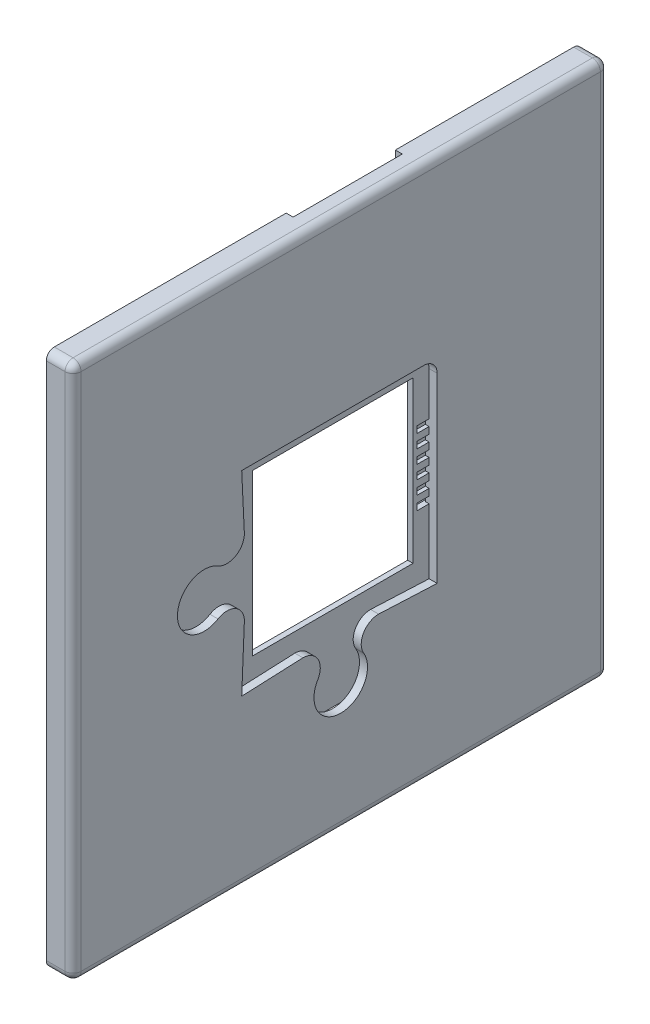
SolidWorks part; units mm, degrees
ref_plane "Front Plane" through (0, 0, 0) normal (0, 0, 1) x (1, 0, 0)
ref_plane "Top Plane" through (0, 0, 0) normal (0, 1, 0) x (1, 0, 0)
ref_plane "Right Plane" through (0, 0, 0) normal (1, 0, 0) x (0, 0, -1)
sketch "Sketch1" plane through (0, 0, 0) normal (1, 0, 0) x (0, 0, -1)
  line L1 (-100, 100) -> (100, 100)
  line L2 (-100, 100) -> (-100, -100)
  line L3 (-100, -100) -> (100, -100)
  line L4 (100, 100) -> (100, -100)
  point P6 (-100, 0)
  dimension "D1" = 200
  dimension "D2" = 200
  dimension "D3" = 100
extrude "Boss-Extrude1" add sketch "Sketch1" along normal blind 10
sketch "Sketch2" plane through (0, 0, 0) normal (-1, 0, 0) x (0, 0, 1)
  line L0 (-35.5, 35.5) -> (-25.5, 35.5)
  line L1 (-35.5, 35.5) -> (-25.5, 35.5)
  line L2 (-35.5, 35.5) -> (-35.5, -35.5)
  line L3 (-35.5, -35.5) -> (35.5, -35.5)
  line L4 (35.5, 35.5) -> (35.5, -35.5)
  line L5 (-25.5, 35.5) -> (-5, 44.5)
  line L6 (-5, 44.5) -> (5, 44.5)
  line L7 (5, 44.5) -> (25.5, 35.5)
  line L8 (25.5, 35.5) -> (35.5, 35.5)
  line L9 (25.5, 35.5) -> (35.5, 35.5)
  line L10 (36.5, 35.5) -> (36.5, -36.5)
  line L11 (-36.5, -36.5) -> (36.5, -36.5)
  line L12 (-36.5, 35.5) -> (-36.5, -36.5)
  line L13 (-35.5, 36.5) -> (-25.5, 36.5)
  line L14 (-25.902, 36.4156) -> (-5.2098, 45.5)
  line L15 (-5.2098, 45.5) -> (5.2098, 45.5)
  line L16 (5.2098, 45.5) -> (25.902, 36.4156)
  line L17 (25.5, 36.5) -> (35.5, 36.5)
  line L18 (-36.5, 35.5) -> (-36.5, 36.5)
  line L19 (-36.5, 36.5) -> (-35.5, 36.5)
  line L20 (35.5, 36.5) -> (36.5, 36.5)
  line L21 (36.5, 36.5) -> (36.5, 35.5)
  point P5 (0, -35.5)
  point P12 (35.5, 0)
  dimension "D1" = 10
  dimension "D2" = 71
  dimension "D3" = 71
  dimension "D4" = 10
  dimension "D5" = 10
  dimension "D6" = 80
  dimension "D7" = 20.5
  dimension "D8" = 1
extrude "Cut-Extrude1" cut sketch "Sketch2" against normal blind 5 contours L21 L20 L17 L16 L15 L14 L13 L19 L18 L12 L11 L10 L7 L8 L4 L3 L2 L0 L5 L6 | L8 L7 L6 L5 L0 L2 L3 L4 region at (0, 2.0136, 0) region at (0, -0.5, 36.3902)
sketch "Sketch3" plane through (5, 0, 0) normal (-1, 0, 0) x (0, 0, 1)
  line L1 (-30, 30) -> (30, 30)
  line L2 (-30, 30) -> (-30, -30)
  line L3 (-30, -30) -> (30, -30)
  line L4 (30, 30) -> (30, -30)
  point P4 (0, -30)
  point P6 (30, 0)
  dimension "D1" = 60
  dimension "D2" = 60
extrude "Cut-Extrude2" cut sketch "Sketch3" against normal through all
sketch "Sketch4" plane through (10, 0, 0) normal (1, 0, 0) x (0, 0, -1)
  line L2 (-36, 35) -> (-36, 14.1421) construction
  line L3 (-36, -37) -> (-14.1421, -37) construction
  line L8 (36, 30) -> (36, -37)
  line L9 (37, -38) -> (-37, -38) construction
  line L10 (-37, 37) -> (37, 37) construction
  line L11 (-37, 37) -> (-37, -38) construction
  line L13 (37, 37) -> (37, -38) construction
  line L14 (14.1421, -37) -> (36, -37) construction
  line L15 (31, 35) -> (-36, 35)
  line L16 (-36, -14.1421) -> (-36, -37) construction
  line L17 (-36, 14.1421) -> (-37, 35)
  line L18 (-37, 35) -> (-36, 35)
  line L19 (-14.1421, -37) -> (-37, -38)
  line L20 (-37, -38) -> (-36, -14.1421)
  line L21 (14.1421, -37) -> (36, -38)
  line L22 (36, -38) -> (36, -37)
  arc A6 (-8.571, -46.8485) -> (8.571, -46.8485) centre (0, -52) ccw
  arc A7 (14.1421, -37) -> (8.571, -46.8485) centre (14.1421, -43.5) ccw
  arc A8 (-8.571, -46.8485) -> (-14.1421, -37) centre (-14.1421, -43.5) ccw
  arc A9 (-45.8485, 8.571) -> (-36, 14.1421) centre (-42.5, 14.1421) ccw
  arc A10 (-36, -14.1421) -> (-45.8485, -8.571) centre (-42.5, -14.1421) ccw
  arc A11 (-45.8485, 8.571) -> (-45.8485, -8.571) centre (-51, 0) ccw
  arc A12 (31, 35) -> (36, 30) centre (31, 30) cw
  point P9 (36, 35)
  point P22 (0.5, -0.5)
  point P24 (0, 0)
  dimension "D3" = 2
  dimension "D4" = 2
  dimension "D6" = 15
  dimension "D8" = 1
  dimension "D9" = 1
  dimension "D12" = 20
  dimension "D13" = 13
  dimension "D14" = 13
  dimension "D7" = 20.8579
  dimension "D5" = 5
  dimension "D1" = 72
  dimension "D2" = 72
  dimension "D10" = 1
  dimension "D11" = 15
  dimension "D15" = 36
extrude "Cut-Extrude3" cut sketch "Sketch4" against normal blind 3
sketch "Sketch8" plane through (0, 0, 0) normal (-1, 0, 0) x (0, 0, 1)
  line L0 (20, 86) -> (-20, 86) construction
  line L1 (10.4, 100) -> (-30.4, 100)
  line L2 (10.4, 100) -> (10.4, 86.4)
  line L3 (10.4, 86.4) -> (-30.4, 86.4)
  line L4 (-30.4, 100) -> (-30.4, 86.4)
  line L5 (-100, -100) -> (-100, 100) construction
  line L6 (-100, 100) -> (100, 100) construction
  dimension "D1" = 0.4
  dimension "D2" = 69.6
  dimension "D3" = 40.8
extrude "Cut-Extrude4" cut sketch "Sketch8" against normal blind 2.6
shell "Shell1" [suppressed] thickness 5
sketch "Sketch9" plane through (0, 0, 0) normal (-1, 0, 0) x (0, 0, 1)
  line L0 (-95, 95) -> (-95, -95)
  line L1 (-95, -95) -> (95, -95)
  line L2 (95, -95) -> (95, 95)
  line L3 (95, 95) -> (15.4, 95)
  line L4 (15.4, 95) -> (15.4, 81.4)
  line L5 (15.4, 81.4) -> (-35.4, 81.4)
  line L6 (-35.4, 81.4) -> (-35.4, 95)
  line L7 (-35.4, 95) -> (-95, 95)
  line L8 (-41.5, 41.5) -> (-41.5, -41.5)
  line L9 (-41.5, -41.5) -> (41.5, -41.5)
  line L10 (41.5, -41.5) -> (41.5, 41.5)
  line L14 (-100, -100) -> (-100, 100) construction
  line L15 (-100, 100) -> (-30.4, 100) construction
  line L16 (-30.4, 100) -> (-30.4, 86.4) construction
  line L17 (10.4, 86.4) -> (10.4, 100) construction
  line L18 (-30.4, 86.4) -> (10.4, 86.4) construction
  line L19 (100, 100) -> (100, -100) construction
  line L20 (100, -100) -> (-100, -100) construction
  line L21 (-36.5, -36.5) -> (-36.5, 36.5) construction
  line L22 (-36.5, -36.5) -> (36.5, -36.5) construction
  line L23 (36.5, 36.5) -> (36.5, -36.5) construction
  line L24 (-5.2098, 45.5) -> (5.2098, 45.5)
  line L27 (-41.5, 41.5) -> (-19.2962, 41.5)
  line L28 (-19.2962, 41.5) -> (-5.6295, 47.5)
  line L29 (-5.6295, 47.5) -> (5.6295, 47.5) construction
  line L30 (5.6295, 47.5) -> (19.2962, 41.5)
  line L32 (19.2962, 41.5) -> (41.5, 41.5)
  line L33 (-36.5, 36.5) -> (-25.7098, 36.5) construction
  line L35 (-25.7098, 36.5) -> (-5.2098, 45.5) construction
  line L36 (5.2098, 45.5) -> (25.7098, 36.5) construction
  line L37 (-5.2098, 45.5) -> (5.2098, 45.5) construction
  line L38 (5.2098, 45.5) -> (25.7098, 36.5) construction
  line L39 (25.7098, 36.5) -> (36.5, 36.5) construction
  line L40 (-25.7098, 36.5) -> (-5.2098, 45.5) construction
  line L41 (-12.5, -41.5) -> (-12.5, -61.5)
  line L42 (-12.5, -61.5) -> (12.5, -61.5)
  line L43 (12.5, -61.5) -> (12.5, -41.5)
  line L44 (41.5, 12.5) -> (61.5, 12.5)
  line L45 (61.5, 12.5) -> (61.5, -12.5)
  line L46 (61.5, -12.5) -> (41.5, -12.5)
  line L47 (-5.2098, 45.5) -> (-5.6295, 47.5)
  line L48 (5.2098, 45.5) -> (5.6295, 47.5)
  point P59 (61.5, 0)
  point P62 (41.5, 0)
  point P63 (0, -61.5)
  point P64 (0, -41.5)
  line M34 (-5.2098, 45.5) -> (5.2098, 45.5)
  dimension "D1" = 5
  dimension "D2" = 5
  dimension "D3" = 5
  dimension "D4" = 5
  dimension "D5" = 5
  dimension "D6" = 5
  dimension "D7" = 5
  dimension "D8" = 5
  dimension "D9" = 5
  dimension "D10" = 5
  dimension "D11" = 5
  dimension "D12" = 5
  dimension "D13" = 2
  dimension "D14" = 2
  dimension "D15" = 5
  dimension "D16" = 2
  dimension "D17" = 25
  dimension "D18" = 25
  dimension "D19" = 20
  dimension "D20" = 20
extrude "Cut-Extrude5" cut sketch "Sketch9" against normal blind 7 contours L6 L7 L0 L1 L2 L3 L4 L5 L45 L46 L10 L9 L43 L42 L41 L8 L27 L28 L29 L30 L32 L44 | L29 L47 L48 M34 region at (0, 92.313, -65.2) region at (0, 46.5129, 0)
fillet "Fillet1" radius 3 8 edges at (5, 100, 100) (5, -100, 100) (10, 0, -100) (10, 100, 0) (10, 0, 100) (10, -100, 0) (5, 100, -100) (5, -100, -100)
sketch "Sketch10" plane through (0, -61.5, 0) normal (0, -1, 0) x (1, 0, 0)
  line L0 (7, -12.5) -> (7, -3.1225) construction
  line L1 (2.7, -2.6) -> (5.8, -2.6)
  line L2 (2.7, -2.6) -> (2.7, 2.6)
  line L3 (2.7, 2.6) -> (5.8, 2.6)
  line L4 (5.8, -2.6) -> (5.8, 2.6)
  line L6 (7, -12.5) -> (0, -12.5) construction
  point P8 (2.7, 0)
  dimension "D1" = 5.2
  dimension "D2" = 3.1
  dimension "D3" = 1.2
  dimension "D4" = 12.5
extrude "Cut-Extrude6" cut sketch "Sketch10" against normal blind 15
fillet "Fillet2" radius 1 4 edges at (4.25, -61.5, -2.6) (5.8, -61.5, 0) (4.25, -61.5, 2.6) (2.7, -61.5, 0)
sketch "Sketch11" plane through (0, 0, 61.5) normal (0, 0, 1) x (1, 0, 0)
  line L1 (2.7, 2.6) -> (5.8, 2.6)
  line L2 (2.7, 2.6) -> (2.7, -2.6)
  line L3 (2.7, -2.6) -> (5.8, -2.6)
  line L4 (5.8, 2.6) -> (5.8, -2.6)
  line L5 (7, -12.5) -> (0, -12.5) construction
  line L6 (7, 12.5) -> (7, -12.5) construction
  point P4 (2.7, 0)
  dimension "D1" = 3.1
  dimension "D2" = 5.2
  dimension "D3" = 12.5
  dimension "D4" = 1.2
extrude "Cut-Extrude7" cut sketch "Sketch11" against normal blind 15
fillet "Fillet3" radius 1 4 edges at (2.7, 0, 61.5) (4.25, -2.6, 61.5) (5.8, 0, 61.5) (4.25, 2.6, 61.5)
fillet "Fillet4" radius 4 4 edges at (3.5, 12.5, 61.5) (3.5, -12.5, 61.5) (3.5, -61.5, 12.5) (3.5, -61.5, -12.5)
sketch "Sketch12" plane through (0, 0, 0) normal (-1, 0, 0) x (0, 0, 1)
  line L0 (-95, 95) -> (-95, -95) construction
  line L1 (-95, -84.8) -> (-99, -84.8)
  line L2 (-95, -84.8) -> (-95, -90)
  line L3 (-95, -90) -> (-99, -90)
  line L4 (-99, -84.8) -> (-99, -90)
  line L5 (-100, -97) -> (-100, 97) construction
  line L6 (97, -100) -> (-97, -100) construction
  dimension "D1" = 1
  dimension "D2" = 10
  dimension "D3" = 5.2
extrude "Cut-Extrude8" cut sketch "Sketch12" against normal blind 2
sketch "Sketch13" plane through (2, 0, 0) normal (-1, 0, 0) x (0, 0, 1)
  line L0 (-99, -90) -> (-95, -90) construction
  line L1 (-99, -84.8) -> (-96, -84.8)
  line L2 (-99, -84.8) -> (-99, -90)
  line L3 (-99, -90) -> (-96, -90)
  line L4 (-96, -84.8) -> (-96, -90)
  dimension "D1" = 3
extrude "Cut-Extrude9" cut sketch "Sketch13" against normal blind 6
sketch "Sketch14" plane through (7, 0, 0) normal (-1, 0, 0) x (0, 0, 1)
  line L0 (95, -95) -> (95, 95) construction
  line L1 (95, -82.4) -> (92, -82.4)
  line L2 (95, -82.4) -> (95, -92.4)
  line L3 (95, -92.4) -> (92, -92.4)
  line L4 (92, -82.4) -> (92, -92.4)
  line L5 (-99, -84.8) -> (-99, -90) construction
  point P8 (-99, -87.4)
  point P9 (92, -87.4)
  dimension "D1" = 10
  dimension "D2" = 3
extrude "Boss-Extrude2" add sketch "Sketch14" along normal blind 7
sketch "Sketch16" plane through (0, 0, 92) normal (0, 0, -1) x (-1, 0, 0)
  line L0 (0, -82.4) -> (0, -92.4) construction
  line L1 (-4.4, -84.9) -> (-1.2, -84.9)
  line L2 (-4.4, -84.9) -> (-4.4, -89.9)
  line L3 (-4.4, -89.9) -> (-1.2, -89.9)
  line L4 (-1.2, -84.9) -> (-1.2, -89.9)
  point P6 (0, -87.4)
  point P7 (-1.2, -87.4)
  dimension "D1" = 3.2
  dimension "D2" = 1.2
  dimension "D3" = 5
extrude "Cut-Extrude10" cut sketch "Sketch16" against normal blind 6
fillet "Fillet5" radius 1 3 edges at (2.8, -89.9, 92) (4.4, -87.4, 92) (2.8, -84.9, 92)
sketch "Sketch17" plane through (0, 0, 0) normal (-1, 0, 0) x (0, 0, 1)
  line L1 (-65.5796, 65.977) -> (65.5796, 65.977)
  line L2 (-65.5796, 65.977) -> (-65.5796, -65.977)
  line L3 (-65.5796, -65.977) -> (65.5796, -65.977)
  line L4 (65.5796, 65.977) -> (65.5796, -65.977)
  point P4 (0, 65.977)
  point P6 (-65.5796, 0)
  dimension "D1" = 131.954
  dimension "D2" = 131.1591
extrude "Cut-Extrude11" cut sketch "Sketch17" against normal blind 2.1
sketch "Sketch18" plane through (0, 0, 0) normal (-1, 0, 0) x (0, 0, 1)
  line L0 (97, -82.4) -> (97, 97)
  line L1 (97, 97) -> (13.4, 97)
  line L2 (13.4, 97) -> (13.4, 83.4)
  line L3 (13.4, 83.4) -> (-33.4, 83.4)
  line L4 (-33.4, 83.4) -> (-33.4, 97)
  line L5 (-33.4, 97) -> (-97, 97)
  line L6 (-97, 97) -> (-97, -84.8)
  line L7 (-97, -90) -> (-97, -97)
  line L28 (-97, -97) -> (97, -97)
  line L30 (15.4, 95) -> (15.4, 81.4) construction
  line L31 (15.4, 81.4) -> (-35.4, 81.4) construction
  line L32 (97, -97) -> (97, -92.4)
  line L33 (-35.4, 95) -> (-95, 95) construction
  line L34 (-95, 95) -> (-95, -84.8) construction
  line L35 (97, -82.4) -> (97, -92.4)
  line L36 (95, -82.4) -> (95, 95) construction
  line L37 (95, -95) -> (95, -92.4) construction
  line L39 (-35.4, 81.4) -> (-35.4, 95) construction
  line L43 (-95, -90) -> (-95, -95) construction
  line L44 (-95, -95) -> (95, -95) construction
  line L47 (95, 95) -> (15.4, 95) construction
  line L48 (15.4, 81.4) -> (-35.4, 81.4)
  line L49 (-35.4, 81.4) -> (-35.4, 95)
  line L50 (-35.4, 95) -> (-95, 95)
  line L51 (-95, 95) -> (-95, -84.8)
  line L55 (-95, -90) -> (-95, -95)
  line L56 (-95, -95) -> (95, -95)
  line L57 (95, -95) -> (95, -92.4)
  line L61 (95, -82.4) -> (95, 95)
  line L62 (15.4, 95) -> (15.4, 81.4)
  line L63 (95, 95) -> (15.4, 95)
  line L64 (-97, -90) -> (-97, -84.8)
  line L65 (-95, -84.8) -> (-95, -90)
  line L66 (95, -82.4) -> (95, -92.4)
  line M19 (-95, -95) -> (-95, -90)
  line M20 (-95, -90) -> (-99, -90)
  line M22 (-99, -84.8) -> (-95, -84.8)
  line M23 (-95, -84.8) -> (-95, 95)
  line M24 (-95, 95) -> (-35.4, 95)
  line M25 (-35.4, 95) -> (-35.4, 81.4)
  line M26 (-35.4, 81.4) -> (15.4, 81.4)
  line M27 (15.4, 81.4) -> (15.4, 95)
  line M28 (15.4, 95) -> (95, 95)
  line M29 (95, 95) -> (95, -82.4)
  line M30 (95, -82.4) -> (92, -82.4)
  line M31 (92, -82.4) -> (92, -92.4)
  line M32 (92, -92.4) -> (95, -92.4)
  line M33 (95, -92.4) -> (95, -95)
  line M34 (95, -95) -> (-95, -95)
  dimension "D1" = 2
extrude "Cut-Extrude12" cut sketch "Sketch18" against normal blind 2 contours L66 L7 L28 L32 L35 L0 L1 L2 L3 L4 L5 L6 M29 M33 M34 M19 M20 M22 M23 M24 M25 M26 M27 M28 | L66 M30 M31 M32 region at (0, -87.4, 96.7256) region at (0, -87.4, 93.5)
sketch "Sketch19" plane through (7, 0, 0) normal (1, 0, 0) x (0, 0, -1)
  line L0 (36, -38) -> (36, 30) construction
  line L1 (36, 13.75) -> (31.5, 13.75)
  line L2 (36, 13.75) -> (36, -13.75)
  line L3 (36, -13.75) -> (31.5, -13.75)
  line L4 (31.5, 13.75) -> (31.5, -13.75)
  line L6 (36, 13.75) -> (31.5, 13.75)
  line L7 (36, 13.75) -> (36, 11.25)
  line L8 (36, 11.25) -> (31.5, 11.25)
  line L9 (31.5, 13.75) -> (31.5, 11.25)
  line L10 (36, 8.75) -> (31.5, 8.75)
  line L11 (36, 8.75) -> (36, 6.25)
  line L12 (36, 6.25) -> (31.5, 6.25)
  line L13 (31.5, 8.75) -> (31.5, 6.25)
  line L14 (36, 3.75) -> (31.5, 3.75)
  line L15 (36, 3.75) -> (36, 1.25)
  line L16 (36, 1.25) -> (31.5, 1.25)
  line L17 (31.5, 3.75) -> (31.5, 1.25)
  line L18 (36, -1.25) -> (31.5, -1.25)
  line L19 (36, -1.25) -> (36, -3.75)
  line L20 (36, -3.75) -> (31.5, -3.75)
  line L21 (31.5, -1.25) -> (31.5, -3.75)
  line L22 (36, -6.25) -> (31.5, -6.25)
  line L23 (36, -6.25) -> (36, -8.75)
  line L24 (36, -8.75) -> (31.5, -8.75)
  line L25 (31.5, -6.25) -> (31.5, -8.75)
  line L26 (36, -11.25) -> (31.5, -11.25)
  line L27 (36, -11.25) -> (36, -13.75)
  line L28 (36, -13.75) -> (31.5, -13.75)
  line L29 (31.5, -11.25) -> (31.5, -13.75)
  line L30 (30, -30) -> (30, 30) construction
  point P25 (31.5, 0)
  line M32 (36, -38) -> (36, 30)
  dimension "D2" = 2.5
  dimension "D3" = 2.5
  dimension "D4" = 2.5
  dimension "D5" = 2.5
  dimension "D6" = 2.5
  dimension "D7" = 2.5
  dimension "D8" = 2.5
  dimension "D9" = 2.5
  dimension "D10" = 2.5
  dimension "D11" = 2.5
  dimension "D12" = 2.5
  dimension "D13" = 1.5
extrude "Cut-Extrude13" cut sketch "Sketch19" against normal through all contours L26 L4 L3 M32 | L24 L2 L22 L4 | L20 L2 L18 L4 | L16 L2 L14 L4 | L12 L2 L10 L4 | L8 L2 L1 L4 region at (7, 12.5, -33.75) region at (7, 7.5, -33.75) region at (7, 2.5, -33.75) region at (7, -2.5, -33.75) region at (7, -7.5, -33.75) region at (7, -12.5, -33.75)
sketch "Sketch20" plane through (2.1, 0, 0) normal (-1, 0, 0) x (0, 0, 1)
  line L0 (-41.5, 41.5) -> (-41.5, -41.5) construction
  line L1 (-31.5, 13.75) -> (-41.5, 13.75)
  line L2 (-31.5, 13.75) -> (-31.5, -13.75)
  line L3 (-31.5, -13.75) -> (-41.5, -13.75)
  line L4 (-41.5, 13.75) -> (-41.5, -13.75)
  line L5 (-31.5, -13.75) -> (-36, -13.75) construction
  line L6 (-31.5, -13.75) -> (-31.5, -11.25) construction
extrude "Cut-Extrude14" cut sketch "Sketch20" against normal blind 3.5
chamfer "Chamfer1" distance 0.6 angle 45 1 edges at (5, 0, -31.5)
sketch "Sketch21" plane through (0, 0, -41.5) normal (0, 0, -1) x (-1, 0, 0)
  line L0 (-5.6, 13.75) -> (-5.6, -13.75) construction
  line L2 (-1.6, 17.75) -> (-1.6, -17.75)
  line L3 (-1.6, -17.75) -> (-5.6, -17.75)
  line L4 (-5.6, 17.75) -> (-5.6, -17.75)
  line L6 (-5.6, -13.75) -> (-2.1, -13.75) construction
  line L7 (0, 22.75) -> (-2.1, 22.75)
  line L8 (0, -97) -> (0, 97) construction
  line L10 (-2.1, 17.75) -> (-1.6, 17.75)
  line L11 (-2.1, 13.75) -> (-2.1, 41.5) construction
  line L12 (-2.1, 17.75) -> (-5.6, 17.75)
  line L13 (0, 22.75) -> (0, -22.75)
  line L14 (-2.1, 22.75) -> (-2.1, 17.75)
  line L16 (-2.1, -17.75) -> (-1.6, -17.75)
  line L17 (-1.6, -17.75) -> (-1.6, 17.75)
  line L18 (-2.1, -17.75) -> (-2.1, -22.75)
  line L19 (-2.1, -41.5) -> (-2.1, -13.75) construction
  line L20 (-2.1, -22.75) -> (0, -22.75)
  line L21 (-5.6, 17.75) -> (-1.6, 17.75)
  line L22 (-1.6, 13.75) -> (-2.1, 13.75)
  line L23 (-2.1, -13.75) -> (-1.6, -13.75)
  line L24 (-2.1, 13.75) -> (-2.1, 17.75)
  line L25 (-2.1, -36.5) -> (-2.1, 36.5) construction
  line L26 (-5.6, 13.75) -> (-2.1, 13.75) construction
  point P14 (-2.1247, -17.75)
  point P15 (-2.1, -22.75)
  point P19 (-2.1, 13.6807)
  point P22 (-2.1, -17.75)
  point P26 (-3.6, -17.75)
  point P27 (-1.6, 13.6807)
  point P28 (-2.1, 13.6807)
  point P30 (-2.1, 13.7638)
  point P38 (-1.6, 13.6797)
  point P39 (-2.1, 13.5733)
  point P40 (-1.6, 13.7414)
  point P41 (-2.1, 13.7414)
  point P42 (-2.1, 13.7414)
  point P43 (0, 0)
  line M5 (-2.1, -13.75) -> (-5.6, -13.75)
  line M6 (-5.6, -13.75) -> (-5.6, 13.75)
  line M7 (-5.6, 13.75) -> (-2.1, 13.75)
  line M8 (-2.1, 13.75) -> (-2.1, 41.5)
  line M12 (-2.1, -41.5) -> (-2.1, -13.75)
  dimension "D1" = 4
  dimension "D2" = 0.5
  dimension "D3" = 4
  dimension "D4" = 5
  dimension "D5" = 4
  dimension "D6" = 5
  dimension "D7" = 4
  dimension "D8" = 5
extrude "Cut-Extrude15" cut sketch "Sketch21" against normal blind 3 contours L3 L2 M8 M7 M6 M5 M12 | L4 L3 M5 M12 | L4 M7 M8 region at (3.6, 0, -41.5) region at (3.85, 15.75, -41.5) region at (3.85, -15.75, -41.5)
extrude "Boss-Extrude4" add sketch "Sketch21<3>" against normal blind 5 contours L20 L13 L7 L2 L3 M12 M8 | L23 L3 L2 M12 | L2 M8 region at (0.8675, 0, -41.5) region at (1.85, 15.75, -41.5) region at (1.85, -15.75, -41.5)
sketch "Sketch21<3>" plane through (0, 0, -41.5) normal (0, 0, -1) x (-1, 0, 0) same geometry as "Sketch21"
chamfer "Chamfer2" distance 0.5 angle 45 8 edges at (1.85, -13.75, -41.5) (2.1, -15.75, -41.5) (3.85, -17.75, -41.5) (1.6, 0, -41.5) (2.1, 15.75, -41.5) (5.6, 0, -41.5) (1.85, 13.75, -41.5) (3.85, 17.75, -41.5)
sketch "Sketch24" plane through (7, 0, 0) normal (-1, 0, 0) x (0, 0, 1)
  line L0 (-95, 95) -> (95, -95) construction
  line L1 (-95, -95) -> (95, 95) construction
  circle A0 centre (80, -80) radius 5
  circle A1 centre (80, -80) radius 1.25
  circle A2 centre (-80, -80) radius 1.25
  circle A3 centre (-80, -80) radius 5
  dimension "D1" = 10
  dimension "D2" = 2.5
  dimension "D4" = 2.5
  dimension "D5" = 10
  dimension "D3" = 15
  dimension "D6" = 15
extrude "Boss-Extrude5" add sketch "Sketch24" along normal blind 5
mirror "Mirror1" about plane through (0, 0, 0) normal (0, 1, 0) of "Boss-Extrude5"
sketch "Sketch25" plane through (2.1, 0, 0) normal (-1, 0, 0) x (0, 0, 1)
  line L0 (36.5, 36.5) -> (41.5, 41.5) construction
  line L1 (41.5, -41.5) -> (36.5, -36.5) construction
  line L2 (-41.5, -41.5) -> (-36.5, -36.5) construction
  line L3 (-41.5, 41.5) -> (-36.5, 36.5) construction
  line L5 (12.5, -41.5) -> (41.5, -41.5) construction
  line L6 (19.2962, 41.5) -> (41.5, 41.5) construction
  line L7 (-19.2962, 41.5) -> (-41.5, 41.5) construction
  circle A0 centre (-38.5, 38.5) radius 1.25
  circle A1 centre (38.5, 38.5) radius 1.25
  circle A2 centre (38.5, -38.5) radius 1.25
  circle A3 centre (-38.5, -38.5) radius 1.25
  dimension "D1" = 2.5
  dimension "D2" = 2.5
  dimension "D3" = 2.5
  dimension "D4" = 2.5
  dimension "D5" = 3
  dimension "D6" = 3
  dimension "D7" = 3
  dimension "D8" = 3
extrude "Cut-Extrude16" cut sketch "Sketch25" against normal blind 3.5
sketch "Sketch27" plane through (0, 95, 0) normal (0, -1, 0) x (1, 0, 0)
  line L0 (7, -35.4) -> (7, -95) construction
  line L1 (7, -41.5) -> (2, -41.5)
  line L2 (7, -41.5) -> (7, -65.5)
  line L3 (7, -65.5) -> (2, -65.5)
  line L4 (2, -41.5) -> (2, -65.5)
  line L5 (2, -95) -> (2, -35.4) construction
  line L8 (7, -45.5) -> (4.5, -45.5)
  line L9 (7, -45.5) -> (7, -61.5)
  line L10 (7, -61.5) -> (4.5, -61.5)
  line L11 (4.5, -45.5) -> (4.5, -61.5)
  line M5 (2, -35.4) -> (2, -95)
  line M7 (7, -95) -> (7, -35.4)
  dimension "D1" = 24
  dimension "D2" = 2.5
  dimension "D3" = 4
  dimension "D4" = 4
extrude "Boss-Extrude6" add sketch "Sketch27" along normal blind 8 contours L11 L8 L2 L1 L3 L10 M5 M7 region at (3.875, 95, -53.5)
sketch "Sketch28" plane through (2, 0, 0) normal (-1, 0, 0) x (0, 0, 1)
  line L0 (-65.5, 87) -> (-65.5, 95) construction
  line L1 (-61.5, 95) -> (-45.5, 95)
  line L2 (-61.5, 95) -> (-61.5, 90)
  line L3 (-61.5, 90) -> (-45.5, 90)
  line L4 (-45.5, 95) -> (-45.5, 90)
  line L5 (-41.5, 87) -> (-41.5, 95) construction
  line L6 (-95, 95) -> (-65.5, 95) construction
  dimension "D1" = 4
  dimension "D2" = 4
  dimension "D3" = 5
extrude "Cut-Extrude17" cut sketch "Sketch28" against normal up to next
sketch "Sketch30" plane through (7, 0, 0) normal (-1, 0, 0) x (0, 0, 1)
  line L0 (15.4, 95) -> (95, 95) construction
  line L1 (41.5, -41.5) -> (95, -95) construction
  line L3 (-95, -95) -> (95, -95) construction
  line L4 (-41.5, -41.5) -> (-95, -95) construction
  line L5 (-95, 95) -> (-41.5, 41.5) construction
  line L7 (-82, -84.5826) -> (-78, -84.5826)
  line L10 (95, -82.4) -> (95, 95) construction
  line L11 (84.5826, 82) -> (95, 82)
  line L12 (84.5826, 82) -> (84.5826, 78)
  line L13 (84.5826, 78) -> (95, 78)
  line L14 (95, 82) -> (95, 78)
  line L15 (95, 95) -> (15.4, 95) construction
  line L16 (78, 84.5826) -> (82, 84.5826)
  line L17 (78, 84.5826) -> (78, 95)
  line L18 (78, 95) -> (82, 95)
  line L19 (82, 84.5826) -> (82, 95)
  line L20 (-95, -95) -> (-95, 95) construction
  line L21 (-75.4174, 78) -> (-95, 78)
  line L22 (-75.4174, 78) -> (-75.4174, 82)
  line L23 (-75.4174, 82) -> (-95, 82)
  line L24 (-95, 78) -> (-95, 82)
  line L25 (95, -95) -> (-95, -95) construction
  line L26 (-82, 75.4174) -> (-78, 75.4174)
  line L27 (-82, 75.4174) -> (-82, -75.4174)
  line L28 (-82, -75.4174) -> (-78, -75.4174)
  line L29 (-78, 75.4174) -> (-78, -75.4174)
  line L30 (82, 75.4174) -> (78, 75.4174)
  line L31 (82, 75.4174) -> (82, -75.4174)
  line L32 (82, -75.4174) -> (78, -75.4174)
  line L33 (78, 75.4174) -> (78, -75.4174)
  line L34 (-75.4174, -78) -> (75.4174, -78)
  line L35 (-75.4174, -78) -> (-75.4174, -82)
  line L36 (-75.4174, -82) -> (75.4174, -82)
  line L37 (75.4174, -78) -> (75.4174, -82)
  line L38 (-41.5, -41.5) -> (-37.5, -41.5)
  line L39 (-41.5, -41.5) -> (-41.5, -95)
  line L40 (-41.5, -95) -> (-37.5, -95)
  line L41 (-37.5, -41.5) -> (-37.5, -95)
  line L42 (-95, 95) -> (-95, -95) construction
  line L43 (-41.5, -41.5) -> (-95, -41.5)
  line L44 (-41.5, -41.5) -> (-41.5, -37.5)
  line L45 (-41.5, -37.5) -> (-95, -37.5)
  line L46 (-95, -41.5) -> (-95, -37.5)
  line L48 (41.5, -41.5) -> (37.5, -41.5)
  line L49 (41.5, -41.5) -> (41.5, -95)
  line L50 (41.5, -95) -> (37.5, -95)
  line L51 (37.5, -41.5) -> (37.5, -95)
  line L52 (-41.5, 41.5) -> (-19.2962, 41.5) construction
  line L53 (41.5, -41.5) -> (95, -41.5)
  line L54 (41.5, -41.5) -> (41.5, -37.5)
  line L55 (41.5, -37.5) -> (95, -37.5)
  line L56 (95, -41.5) -> (95, -37.5)
  line L57 (-82, 41.5) -> (-95, 41.5)
  line L58 (-82, 41.5) -> (-82, 37.5)
  line L59 (-82, 37.5) -> (-95, 37.5)
  line L60 (-95, 41.5) -> (-95, 37.5)
  line L61 (41.5, 41.5) -> (95, 41.5)
  line L62 (41.5, 41.5) -> (41.5, 37.5)
  line L63 (41.5, 37.5) -> (95, 37.5)
  line L64 (95, 41.5) -> (95, 37.5)
  line L65 (41.5, 41.5) -> (37.5, 41.5)
  line L66 (41.5, 41.5) -> (41.5, 95)
  line L67 (41.5, 95) -> (37.5, 95)
  line L68 (37.5, 41.5) -> (37.5, 95)
  line L69 (-82, -84.5826) -> (-82, -95)
  line L70 (41.5, 82) -> (75.4174, 82)
  line L71 (41.5, 82) -> (41.5, 78)
  line L72 (41.5, 78) -> (75.4174, 78)
  line L73 (75.4174, 82) -> (75.4174, 78)
  line L74 (-82, -95) -> (-78, -95)
  line L75 (-78, -84.5826) -> (-78, -95)
  line L76 (-65.5, 95) -> (-95, 95) construction
  line L77 (-75.4174, -78) -> (-95, -78)
  line L78 (-75.4174, -78) -> (-75.4174, -82)
  line L79 (-75.4174, -82) -> (-95, -82)
  line L80 (-95, -78) -> (-95, -82)
  line L81 (-82, 95) -> (-78, 95)
  line L82 (-82, 95) -> (-82, 84.5826)
  line L83 (-82, 84.5826) -> (-78, 84.5826)
  line L84 (-78, 95) -> (-78, 84.5826)
  line L86 (84.5826, -78) -> (95, -78)
  line L87 (84.5826, -78) -> (84.5826, -82)
  line L88 (84.5826, -82) -> (95, -82)
  line L89 (95, -78) -> (95, -82)
  circle A0 centre (80, 80) radius 5 construction
  circle A1 centre (80, 80) radius 5 construction
  circle A2 centre (-80, 80) radius 5 construction
  circle A3 centre (-80, 80) radius 5 construction
  circle A4 centre (-80, 80) radius 5 construction
  circle A5 centre (-80, -80) radius 5 construction
  circle A6 centre (80, -80) radius 5 construction
  circle A7 centre (-80, -80) radius 5 construction
  circle A8 centre (80, -80) radius 5 construction
  circle A9 centre (-80, 80) radius 5 construction
  point P85 (41.5, -95)
  circle M1 centre (80, 80) radius 5
  circle M2 centre (-80, -80) radius 5
  circle M3 centre (80, -80) radius 5
  line M8 (-12.5, -41.5) -> (-41.5, -41.5)
  line M9 (-41.5, -41.5) -> (-41.5, 41.5)
  line M16 (19.2962, 41.5) -> (41.5, 41.5)
  line M17 (41.5, 41.5) -> (41.5, 12.5)
  line M23 (41.5, -12.5) -> (41.5, -41.5)
  line M24 (41.5, -41.5) -> (12.5, -41.5)
  circle M33 centre (-80, 80) radius 5
  line M36 (-65.5, 95) -> (-95, 95)
  line M37 (-95, 95) -> (-95, -95)
  line M38 (-95, -95) -> (95, -95)
  line M43 (95, -82.4) -> (95, 95)
  line M44 (95, 95) -> (15.4, 95)
  dimension "D2" = 4
  dimension "D3" = 4
  dimension "D4" = 4
  dimension "D5" = 4
  dimension "D6" = 4
  dimension "D7" = 4
  dimension "D8" = 4
  dimension "D9" = 4
  dimension "D10" = 4
  dimension "D11" = 4
  dimension "D12" = 4
  dimension "D13" = 4
  dimension "D14" = 4
  dimension "D15" = 4
  dimension "D16" = 4
  dimension "D17" = 4
  dimension "D18" = 4
  dimension "D19" = 4
extrude "Boss-Extrude8" add sketch "Sketch30" along normal blind 2.5 contours L34 L49 L36 M3 | L55 L53 L33 M23 | L55 L33 L53 L31 | L53 L33 L31 M3 | L55 L31 L53 M43 | L63 L33 L55 L31 | L51 L34 L49 M24 | L36 L51 L49 M38 | L51 L34 L41 L36 | L41 L36 L39 M38 | L39 L34 L36 M2 | L41 L39 L34 M8 | L41 L34 L39 L36 | L34 L51 L36 L49 | L45 L29 L43 M9 | L29 L45 L27 L43 | L27 L45 L43 M37 | L45 L29 L27 M33 | L23 L21 M33 M37 | L59 L27 L57 M37 | L29 L43 L27 M2 | L68 L66 M16 M44 | L63 L33 L61 M17 | L33 L63 L31 L61 | L31 L63 L61 M43 | L33 L61 L31 M1 | L66 L72 L70 M1 | L13 L11 M1 M43 | L19 L17 M1 M44 | L79 L77 M2 M37 | L75 L69 M2 M38 | L88 L86 M3 M43 | L84 L82 M36 M33 | L53 L56 L55 L54 | L29 L28 L27 L26 | L59 L60 L57 L58 | L66 L67 L68 L65 region at (7, -89.9309, -80) region at (7, -80, -89.9309) region at (7, -80, -58.3186) region at (7, -88.5, -39.5) region at (7, -80, -39.5) region at (7, -58.3186, -80) region at (7, -59.75, -39.5) region at (7, -80, 0) region at (7, -39.5, -88.5) region at (7, -39.5, -80) region at (7, -88.5, 39.5) region at (7, -39.5, -59.75) region at (7, -80, 39.5) region at (7, 18.8184, -80) region at (7, -59.75, 39.5) region at (7, -80, 58.3186) region at (7, 39.5, -88.5) region at (7, -39.5, 59.75) region at (7, -80, 89.9309) region at (7, 80, -89.9309) region at (7, -58.3186, 80) region at (7, -39.5, 80) region at (7, 0, 80) region at (7, -39.5, 88.5) region at (7, 89.9309, -80) region at (7, 39.5, 59.75) region at (7, 39.5, 80) region at (7, 58.3186, 80) region at (7, 39.5, 88.5) region at (7, 68.25, 39.5) region at (7, 80, 58.3186) region at (7, 80, 89.9309) region at (7, 89.9309, 80)
fillet "Fillet10" radius 3 91 edges at (5.75, 37.5, 95) (4.5, -82.4, 95) (4.5, -95, -95) (5.75, -41.5, -78) (5.75, -37.5, -78) (5.75, -41.5, -37.5) (5.75, -82, 37.5) (5.75, -41.5, 37.5) (5.75, -78, 37.5) (5.75, -95, 37.5) (5.75, -95, 41.5) (5.75, -82, 41.5) (5.75, -78, 41.5) (5.75, -37.5, 41.5) (5.75, -41.5, 41.5) (5.75, -37.5, 95) (5.75, -41.5, 95) (5.75, -78, 75.4174) (5.75, -82, 75.4174) (5.75, -75.4174, 82) (5.75, -75.4174, 78) (5.75, -41.5, 82) (5.75, -41.5, 78) (5.75, -37.5, 82) (5.75, -37.5, 78) (4.55, -12.5, 41.5) (4.55, 12.5, 41.5) (5.75, 41.5, 37.5) (5.75, 37.5, 41.5) (5.75, 41.5, 41.5) (5.75, 37.5, 78) (5.75, 37.5, 82) (5.75, 41.5, 78) (5.75, 41.5, 82) (5.75, 41.5, 95) (5.75, 78, 41.5) (5.75, 82, 41.5) (5.75, 95, 41.5) (5.75, 82, 95) (4.5, 95, 95) (5.75, 78, 95) (5.75, 82, 84.5826) (5.75, 84.5826, 82) (5.75, 78, 84.5826) (5.75, 95, 82) (5.75, 75.4174, 82) (5.75, 75.4174, 78) (5.75, 78, 75.4174) (5.75, 82, 75.4174) (5.75, 84.5826, 78) (5.75, 95, 78) (5.75, 95, 37.5) (4.5, 95, 15.4) (4.5, 81.4, 15.4) (4.5, 81.4, -35.4) (4.5, 95, -35.4) (4.5, 87, -41.5) (4.5, 95, -41.5) (5.75, 41.5, -95) (5.75, 82, -95) (5.75, -78, -41.5) (5.75, -37.5, -41.5) (5.75, -41.5, -41.5) (5.75, -82, -41.5) (5.75, -95, -41.5) (5.75, -75.4174, -82) (5.75, -75.4174, -78) (5.75, -78, -75.4174) (5.75, -82, -75.4174) (5.75, 37.5, -95) (5.75, 78, -95) (4.5, 95, -95) (5.75, -37.5, -95) (5.75, -37.5, -82) (5.75, -41.5, -95) (5.75, -41.5, -82) (5.75, 37.5, -82) (5.75, 41.5, -82) (5.75, 75.4174, -78) (5.75, 75.4174, -82) (5.75, 78, -84.5826) (5.75, 82, -84.5826) (5.75, -78, -37.5) (5.75, -82, -37.5) (5.75, -84.5826, -78) (5.75, -78, -84.5826) (5.75, -84.5826, -82) (5.75, -82, -84.5826) (4.5, 87, -65.5) (5.75, 95, -78) (5.75, 95, -82)
sketch "Sketch31" plane through (2.6, 0, 0) normal (-1, 0, 0) x (0, 0, 1)
  circle A0 centre (10, 89) radius 1.25
  circle A1 centre (-10, 89) radius 1.25
  dimension "D1" = 2.5
  dimension "D2" = 2.5
extrude "Cut-Extrude18" cut sketch "Sketch31" against normal blind 5
fillet "Fillet11" radius 3 1 edges at (7, 95, -53.5)
